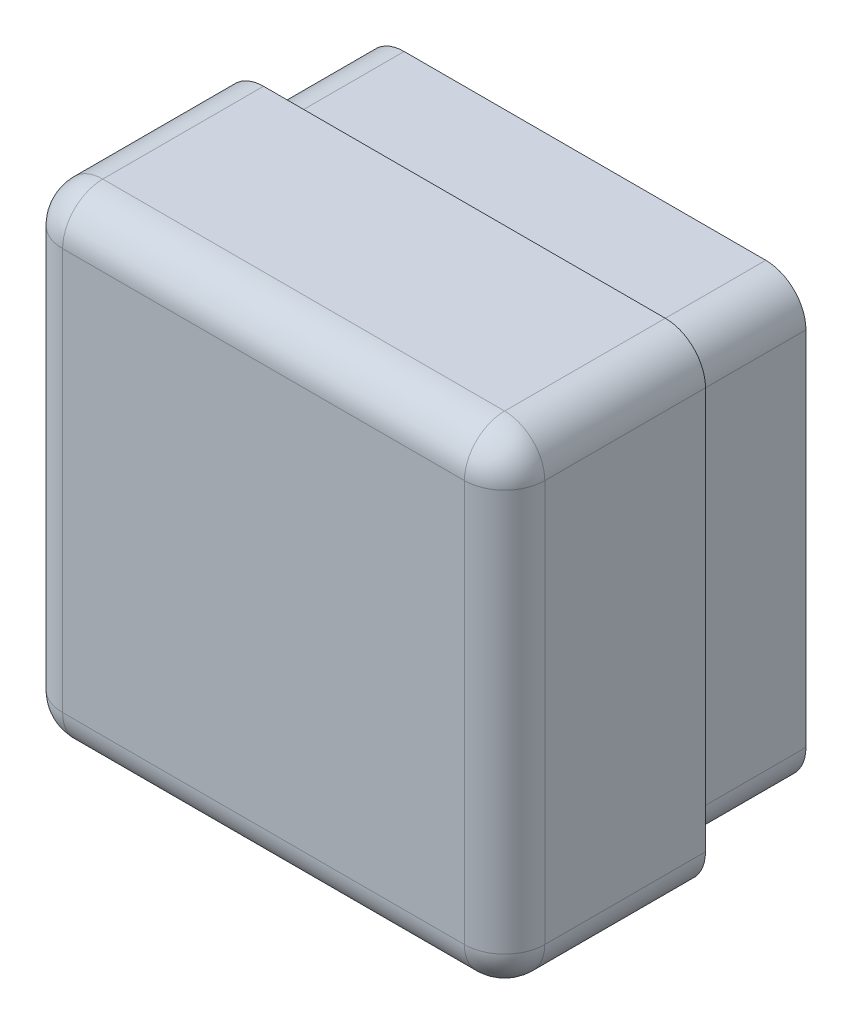
SolidWorks part; units mm, degrees
material "Gray Cast Iron"
ref_plane "Front Plane" through (0, 0, 0) normal (0, 0, 1) x (1, 0, 0)
ref_plane "Top Plane" through (0, 0, 0) normal (0, 1, 0) x (1, 0, 0)
ref_plane "Right Plane" through (0, 0, 0) normal (1, 0, 0) x (0, 0, -1)
sketch "Sketch2" plane through (0, 0, 0) normal (0, 0, 1) x (1, 0, 0)
  line L1 (-60, -60) -> (60, -60)
  line L2 (-60, -60) -> (-60, 60)
  line L3 (-60, 60) -> (60, 60)
  line L4 (60, -60) -> (60, 60)
  line L5 (-60, -60) -> (60, 60) construction
  line L6 (-60, 60) -> (60, -60) construction
  point P0 (0, 0)
  dimension "D1" = 120
  dimension "D2" = 120
extrude "Boss-Extrude1" add sketch "Sketch2" along normal blind 80 contours L2 L1 L4 L3
fillet "Fillet1" radius 10 4 edges at (60, 0, 80) (0, -60, 80) (-60, 0, 80) (0, 60, 80)
fillet "Fillet3" radius 10 8 edges at (-57.0711, -57.0711, 77.0711) (57.0711, -57.0711, 77.0711) (57.0711, 57.0711, 77.0711) (-57.0711, 57.0711, 77.0711) (-60, -60, 35) (60, -60, 35) (60, 60, 35) (-60, 60, 35)
sketch "Sketch6" plane through (0, 0, 0) normal (0, 0, -1) x (-1, 0, 0)
  line L1 (-45, -55) -> (45, -55)
  line L2 (-55, -45) -> (-55, 45)
  line L3 (-45, 55) -> (45, 55)
  line L4 (55, -45) -> (55, 45)
  line L5 (-55, -55) -> (55, 55) construction
  line L6 (-55, 55) -> (55, -55) construction
  line L7 (-50, -60) -> (50, -60)
  line L8 (-60, -50) -> (-60, 50)
  line L9 (-50, 60) -> (50, 60)
  line L10 (60, -50) -> (60, 50)
  line L11 (-60, -60) -> (60, 60) construction
  line L12 (-60, 60) -> (60, -60) construction
  arc A0 (-45, -55) -> (-55, -45) centre (-45, -45) cw
  arc A1 (45, -55) -> (55, -45) centre (45, -45) ccw
  arc A2 (45, 55) -> (55, 45) centre (45, 45) cw
  arc A3 (-55, 45) -> (-45, 55) centre (-45, 45) cw
  arc A4 (-50, -60) -> (-60, -50) centre (-50, -50) cw
  arc A5 (50, -60) -> (60, -50) centre (50, -50) ccw
  arc A6 (50, 60) -> (60, 50) centre (50, 50) cw
  arc A7 (-60, 50) -> (-50, 60) centre (-50, 50) cw
  point P0 (0, 0)
  point P18 (0, 0)
  dimension "D3" = 10
  dimension "D6" = 10
  dimension "D1" = 110
  dimension "D2" = 110
  dimension "D4" = 120
  dimension "D5" = 120
extrude "Cut-Extrude5" cut sketch "Sketch6" against normal blind 30 contours A7 L9 A6 L10 A5 L7 A4 L8 | A3 L2 A0 L1 A1 L4 A2 L3
shell "Shell2" thickness 5 removed face at (0, 0, 0)
